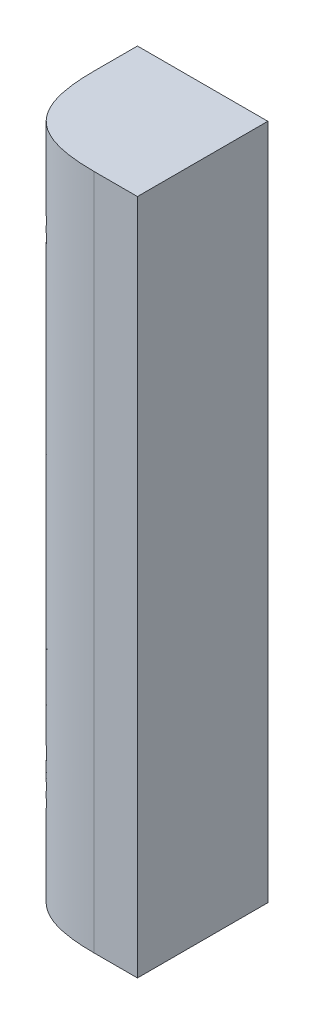
SolidWorks part; units mm, degrees
ref_plane "Front Plane" through (0, 0, 0) normal (0, 0, 1) x (1, 0, 0)
ref_plane "Top Plane" through (0, 0, 0) normal (0, 1, 0) x (1, 0, 0)
ref_plane "Right Plane" through (0, 0, 0) normal (1, 0, 0) x (0, 0, -1)
sketch "Sketch1" plane through (0, 0, 0) normal (0, 1, 0) x (1, 0, 0)
  line L1 (0, 0) -> (36, 0)
  line L2 (0, 0) -> (0, 36)
  line L3 (0, 36) -> (36, 36)
  line L4 (36, 0) -> (36, 36)
  dimension "D1" = 36
  dimension "D2" = 36
extrude "Boss-Extrude1" add sketch "Sketch1" along normal blind 186.9
fillet "Fillet1" radius 24 1 edges at (0, 93.45, 0) conic rho 0.55
sketch "Sketch2" plane through (0, 0, 0) normal (0, -1, 0) x (1, 0, 0)
  line L0 (36, -36) -> (0, -36) construction
  line L2 (36, 0) -> (36, -36) construction
  line L3 (24, 0) -> (36, 0) construction
  circle A0 centre (18, -18) radius 2
  dimension "D1" = 4
  dimension "D2" = 18
  dimension "D3" = 18
extrude "Cut-Extrude1" cut sketch "Sketch2" against normal blind 5
sketch "Sketch3" plane through (0, 0, 0) normal (0, -1, 0) x (1, 0, 0)
  line L0 (36, 0) -> (36, -36) construction
  line L1 (26, -5) -> (31, -5)
  line L2 (26, -5) -> (26, -26)
  line L3 (26, -31) -> (31, -31)
  line L4 (31, -5) -> (31, -31)
  line L5 (24, 0) -> (36, 0) construction
  line L6 (36, -36) -> (0, -36) construction
  line L7 (0, -36) -> (0, -24) construction
  line L8 (5, -31) -> (26, -31)
  line L9 (5, -31) -> (5, -26)
  line L10 (5, -26) -> (26, -26)
  line L13 (9, -9) -> (14, -9)
  line L14 (9, -9) -> (9, -14)
  line L15 (9, -14) -> (14, -14)
  line L16 (14, -9) -> (14, -14)
  dimension "D7" = 5
  dimension "D8" = 5
  dimension "D9" = 12
  dimension "D1" = 5
  dimension "D2" = 5
  dimension "D3" = 5
  dimension "D4" = 5
  dimension "D5" = 5
  dimension "D6" = 5
  dimension "D10" = 12
  dimension "D11" = 9
  dimension "D12" = 9
extrude "Boss-Extrude2" add sketch "Sketch3" along normal blind 4
